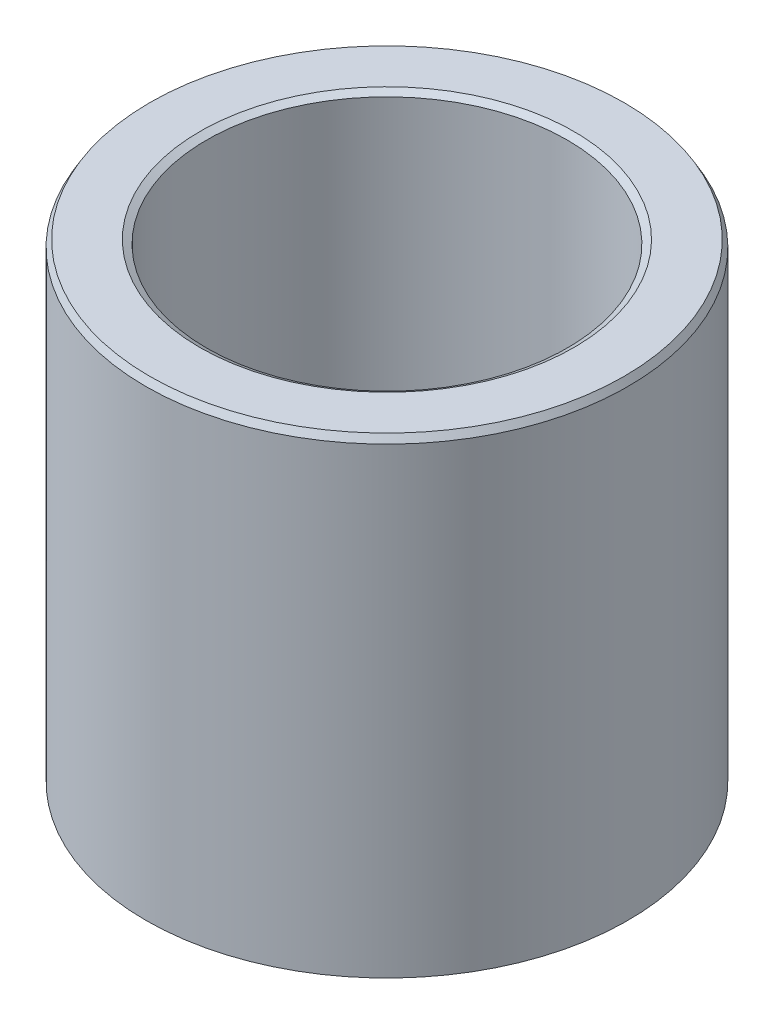
SolidWorks part; units mm, degrees
ref_plane "Front Plane" through (0, 0, 0) normal (0, 0, 1) x (1, 0, 0)
ref_plane "Top Plane" through (0, 0, 0) normal (0, 1, 0) x (1, 0, 0)
ref_plane "Right Plane" through (0, 0, 0) normal (1, 0, 0) x (0, 0, -1)
sketch "Sketch1" plane through (0, 0, 0) normal (0, 1, 0) x (1, 0, 0)
  circle A0 centre (0, 0) radius 52.5
  dimension "SLEEVE_OD" = 105
extrude "Boss-Extrude1" add sketch "Sketch1" along normal blind 103.0346
sketch "Sketch2" plane through (0, 0, 0) normal (0, 1, 0) x (1, 0, 0)
  circle A0 centre (0, 0) radius 39.2644
  dimension "BORE_D" = 78.5288
extrude "Cut-Extrude1" cut sketch "Sketch2" along normal through all
chamfer "Chamfer1" distance 1.4824 angle 30 4 edges at (0, 103.0346, 39.2644) (0, 0, 39.2644) (0, 0, 52.5) (0, 103.0346, 52.5) first distance on face at (0, 103.0346, 39.2644) first distance on face at (0, 0, 39.2644) first distance on face at (0, 103.0346, 52.5)
